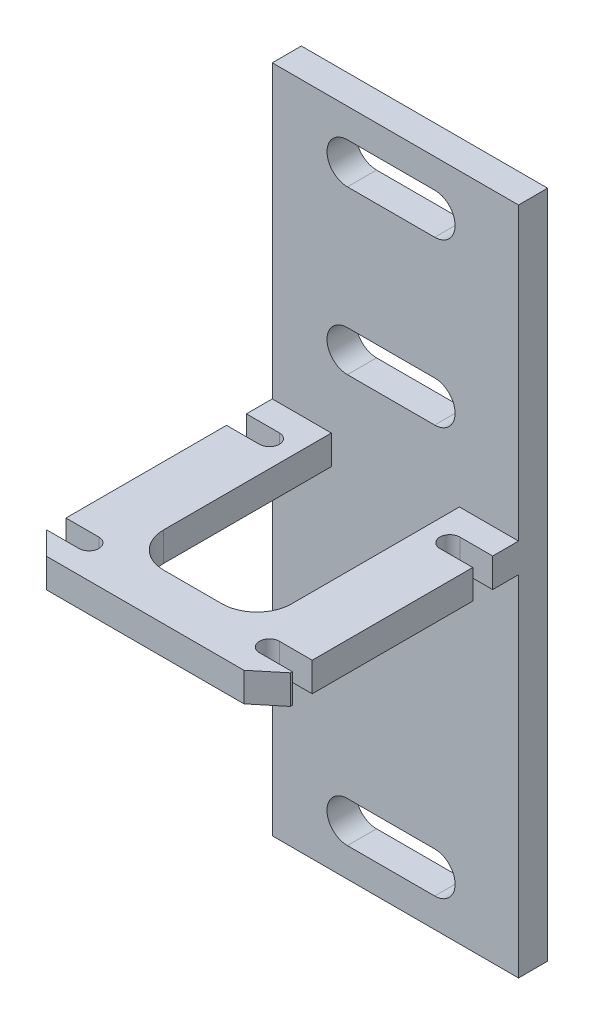
SolidWorks part; units mm, degrees
ref_plane "Front Plane" through (0, 0, 0) normal (0, 0, 1) x (1, 0, 0)
ref_plane "Top Plane" through (0, 0, 0) normal (0, 1, 0) x (1, 0, 0)
ref_plane "Right Plane" through (0, 0, 0) normal (1, 0, 0) x (0, 0, -1)
sketch "Sketch1" plane through (0, 0, 0) normal (0, 1, 0) x (1, 0, 0)
  line L1 (-10.2553, 3.0084) -> (11.7447, 3.0084)
  line L2 (-20.4053, 3.0084) -> (-20.4053, -4.9916)
  line L3 (-20.4053, -4.9916) -> (21.8947, -4.9916)
  line L4 (21.8947, 3.0084) -> (21.8947, -4.9916)
  line L5 (0, 0) -> (21.8947, -4.9916) construction
  line L6 (-20.4053, -4.9916) -> (0, 0) construction
  line L8 (-20.4053, 3.0084) -> (-20.4053, 42.8084)
  line L9 (-20.4053, 42.8084) -> (-10.2553, 42.8084)
  line L10 (-10.2553, 3.0084) -> (-10.2553, 42.8084)
  line L12 (21.8947, 3.0084) -> (21.8947, 42.8084)
  line L13 (21.8947, 42.8084) -> (11.7447, 42.8084)
  line L14 (11.7447, 3.0084) -> (11.7447, 42.8084)
  point P0 (0, 0)
  dimension "D1" = 42.3
  dimension "D2" = 47.8
  dimension "D3" = 22
  dimension "D4" = 8
  dimension "D5" = 4.9916
extrude "Boss-Extrude1" add sketch "Sketch1" along normal blind 5
sketch "Sketch2" plane through (0, 0, 0) normal (0, -1, 0) x (1, 0, 0)
  line L0 (-20.4053, -33.3684) -> (-14.7553, -33.3684)
  line L1 (-20.4053, 4.9916) -> (21.8947, 4.9916) construction
  line L2 (21.8947, 4.9916) -> (21.8947, -42.8084) construction
  line L3 (-20.4053, -29.9484) -> (-14.7553, -29.9484)
  line L4 (-20.4053, -2.3684) -> (-14.7553, -2.3684)
  line L5 (-20.4053, 1.0516) -> (-14.7553, 1.0516)
  line L6 (21.8947, 1.0516) -> (16.2447, 1.0516)
  line L7 (21.8947, -2.3684) -> (16.2447, -2.3684)
  line L8 (21.8947, -29.9484) -> (16.2447, -29.9484)
  line L9 (21.8947, -33.3684) -> (16.2447, -33.3684)
  line L10 (-20.4053, -42.8084) -> (-20.4053, 4.9916) construction
  line L11 (21.8947, 4.9916) -> (21.8947, -42.8084) construction
  line L12 (-20.4053, -33.3684) -> (-20.4053, -29.9484)
  line L13 (21.8947, 1.0516) -> (21.8947, -2.3684)
  line L14 (21.8947, -29.9484) -> (21.8947, -33.3684)
  line L15 (-20.4053, -2.3684) -> (-20.4053, 1.0516)
  arc A0 (-14.7553, -33.3684) -> (-14.7553, -29.9484) centre (-14.7553, -31.6584) ccw
  arc A1 (-14.7553, -2.3684) -> (-14.7553, 1.0516) centre (-14.7553, -0.6584) ccw
  arc A2 (16.2447, 1.0516) -> (16.2447, -2.3684) centre (16.2447, -0.6584) ccw
  arc A3 (16.2447, -29.9484) -> (16.2447, -33.3684) centre (16.2447, -31.6584) ccw
  dimension "D5" = 3.42
  dimension "D1" = 31
  dimension "D2" = 31
  dimension "D3" = 5.65
  dimension "D4" = 5.65
extrude "Cut-Extrude1" cut sketch "Sketch2" against normal through all
fillet "Fillet1" radius 6 2 edges at (-10.2553, 2.5, -3.0084) (11.7447, 2.5, -3.0084)
sketch "Sketch3" plane through (0, 0, 0) normal (0, -1, 0) x (1, 0, 0)
  line L0 (21.8947, 1.3913) -> (17.5274, 4.9916)
  line L1 (21.8947, 4.9916) -> (21.8947, 1.0516) construction
  line L2 (-20.4053, 4.9916) -> (21.8947, 4.9916) construction
  line L3 (17.5274, 4.9916) -> (21.8947, 4.9916)
  line L4 (21.8947, 4.9916) -> (21.8947, 1.3913)
  line L5 (-20.4053, 0.9947) -> (-16.3978, 4.9916)
  line L6 (-20.4053, -42.8084) -> (-20.4053, -33.3684) construction
  line L7 (-16.3978, 4.9916) -> (-20.4053, 4.9916)
  line L8 (-20.4053, 4.9916) -> (-20.4053, 0.9947)
  dimension "D1" = 5.66
extrude "Cut-Extrude2" cut sketch "Sketch3" against normal through all
sketch "Sketch5" plane through (0, 5, 0) normal (0, 1, 0) x (1, 0, 0)
  line L0 (21.8947, 42.8084) -> (-10.2553, 42.8084)
  line L1 (21.8947, 42.8084) -> (21.8947, 37.8084)
  line L3 (21.8947, 37.8084) -> (-10.2553, 37.8084)
  line L4 (-10.2553, 42.8084) -> (-20.4053, 42.8084)
  line L6 (-20.4053, 42.8084) -> (-20.4053, 37.8084)
  line L7 (-10.2553, 37.8084) -> (-20.4053, 37.8084)
extrude "Boss-Extrude4" add sketch "Sketch5" against normal blind 65 and the other way blind 50
fillet "Fillet2" [suppressed] radius 1
sketch "Sketch7" plane through (0, 0, -37.8084) normal (0, 0, 1) x (1, 0, 0)
  line L0 (-9.9053, -45) -> (-9.9053, -55) construction
  line L1 (-6.4053, -45) -> (-6.4053, -55)
  line L2 (-13.4053, -45) -> (-13.4053, -55)
  line L3 (11.3947, -45) -> (11.3947, -55) construction
  line L4 (14.8947, -45) -> (14.8947, -55)
  line L5 (7.8947, -45) -> (7.8947, -55)
  line L6 (-20.4053, -60) -> (21.8947, -60) construction
  line L7 (-20.4053, -60) -> (-20.4053, 0) construction
  line L9 (21.8947, -60) -> (21.8947, 0) construction
  arc A0 (-6.4053, -45) -> (-13.4053, -45) centre (-9.9053, -45) ccw
  arc A1 (-13.4053, -55) -> (-6.4053, -55) centre (-9.9053, -55) ccw
  arc A2 (14.8947, -45) -> (7.8947, -45) centre (11.3947, -45) ccw
  arc A3 (7.8947, -55) -> (14.8947, -55) centre (11.3947, -55) ccw
  point P2 (-9.9053, -50)
  point P9 (11.3947, -50)
  dimension "D3" = 3.5
  dimension "D6" = 3.5
  dimension "D1" = 5
  dimension "D2" = 15
  dimension "D4" = 7
  dimension "D5" = 7
  dimension "D7" = 5
  dimension "D8" = 15
extrude "Cut-Extrude4" [suppressed] cut sketch "Sketch7" against normal through all
sketch "Sketch8" plane through (0, 0, -37.8084) normal (0, 0, 1) x (1, 0, 0)
  line L0 (-7.5, 18.56) -> (7.5, 18.56) construction
  line L1 (-7.5, 22.06) -> (7.5, 22.06)
  line L2 (-7.5, 15.06) -> (7.5, 15.06)
  line L3 (7.5, -51.5) -> (-7.5, -51.5) construction
  line L4 (7.5, -55) -> (-7.5, -55)
  line L5 (7.5, -48) -> (-7.5, -48)
  line L6 (-7.5, 46.5) -> (7.5, 46.5) construction
  line L7 (-7.5, 50) -> (7.5, 50)
  line L8 (-7.5, 43) -> (7.5, 43)
  line L9 (-20.4053, 55) -> (21.8947, 55) construction
  line L10 (0, 0) -> (0, 70.027) construction
  line L11 (-20.4053, -60) -> (21.8947, -60) construction
  arc A0 (-7.5, 22.06) -> (-7.5, 15.06) centre (-7.5, 18.56) ccw
  arc A1 (7.5, 15.06) -> (7.5, 22.06) centre (7.5, 18.56) ccw
  arc A2 (7.5, -55) -> (7.5, -48) centre (7.5, -51.5) ccw
  arc A3 (-7.5, -48) -> (-7.5, -55) centre (-7.5, -51.5) ccw
  arc A4 (-7.5, 50) -> (-7.5, 43) centre (-7.5, 46.5) ccw
  arc A5 (7.5, 43) -> (7.5, 50) centre (7.5, 46.5) ccw
  point P2 (0, 18.56)
  point P9 (0, -51.5)
  point P18 (0, 46.5)
  dimension "D1" = 3.5
  dimension "D3" = 3.5
  dimension "10" = 5
  dimension "D4" = 0
  dimension "D5" = 0
  dimension "D6" = 15
  dimension "D7" = 15
  dimension "D8" = 5
  dimension "D2" = 2
extrude "Cut-Extrude5" cut sketch "Sketch8" against normal blind 10
equation "\"26..50mm\"=27"
